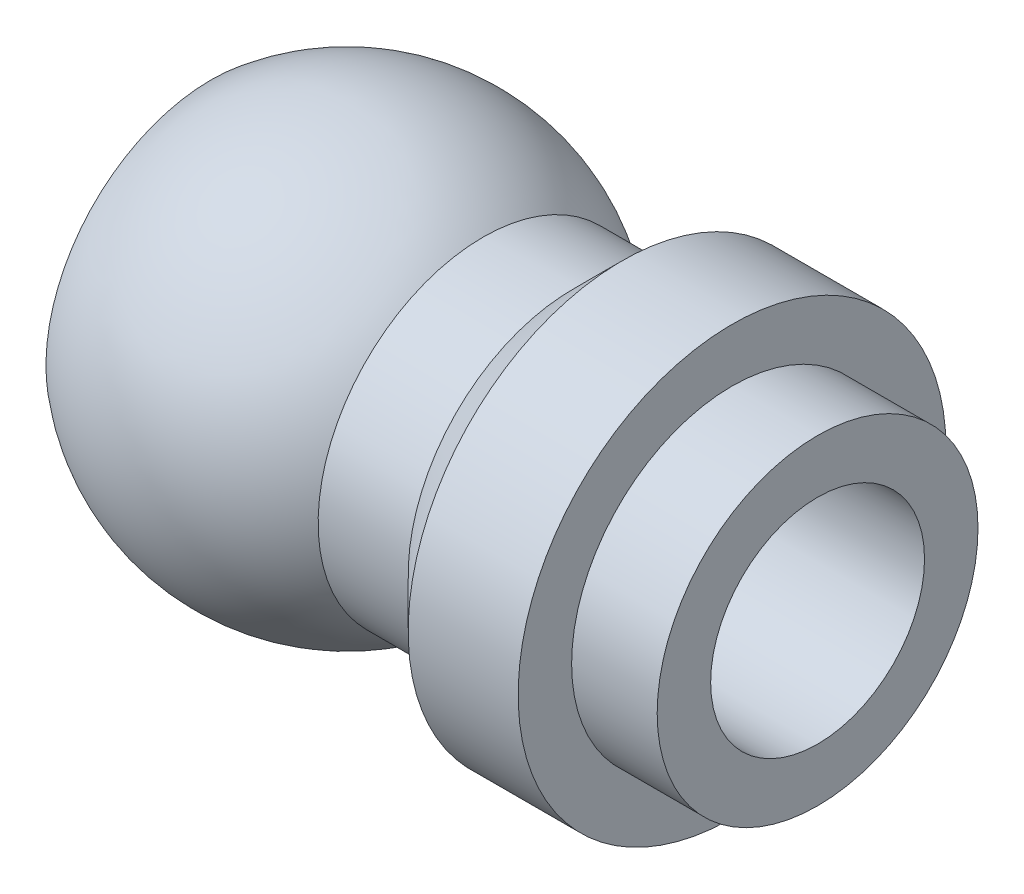
SolidWorks part; units mm, degrees
ref_plane "Front Plane" through (0, 0, 0) normal (0, 0, 1) x (1, 0, 0)
ref_plane "Top Plane" through (0, 0, 0) normal (0, 1, 0) x (1, 0, 0)
ref_plane "Right Plane" through (0, 0, 0) normal (1, 0, 0) x (0, 0, -1)
sketch "Sketch1" plane through (0, 0, 0) normal (0, 0, 1) x (1, 0, 0)
  line L0 (0, 0) -> (0, 4.8986)
  line L1 (8.0812, 4.8986) -> (10.7535, 4.8986)
  line L2 (10.7535, 4.8986) -> (12.2049, 6.35)
  line L3 (12.2049, 6.35) -> (15.4706, 6.35)
  line L4 (15.4706, 6.35) -> (15.4706, 4.7625)
  line L5 (15.4706, 4.7625) -> (18.0106, 4.7625)
  line L6 (18.0106, 4.7625) -> (18.0106, 0)
  line L7 (18.0106, 0) -> (0, 0)
  arc A0 (0, 4.8986) -> (8.0812, 4.8986) centre (4.0406, 0) cw
  point P11 (16.7406, 4.7625)
  dimension "D6" = 6.35
  dimension "D1" = 6.35
  dimension "D2" = 1.5875
  dimension "D3" = 2.54
  dimension "D4" = 4.8986
  dimension "D5" = 135
  dimension "D7" = 11.43
  dimension "D8" = 3.2657
revolve "Revolve1" add sketch "Sketch1" angle 360 about L7
ref_axis "Axis1" through (-0.9011, 0, 0) along (1, 0, 0)
ref_axis "Axis2" through (0, 0, -6.985) along (0, 0, 1)
hole_wizard "1/4 (0.25) Diameter Hole1" positions "Sketch2" profile "Sketch3" hole size "1/4" standard "ANSI Inch" end condition through all
sketch "Sketch2" plane through (0, 0, 0) normal (-1, 0, 0) x (0, 0, 1)
  point P0 (0, 0)
sketch "Sketch3" plane through (0, 0, 0) normal (0, 1, 0) x (0, 0, 1)
  line L0 (0, 0) -> (0, 18.0106)
  line L1 (0, 18.0106) -> (3.175, 18.0106)
  line L2 (3.175, 18.0106) -> (3.175, 0)
  line L5 (3.175, 0) -> (0, 0)
  line L11 (0, -6.35) -> (0, 107.95) construction
  dimension "Thru Hole Dia." = 6.35
  dimension "Thru Hole Depth" = 18.0106
